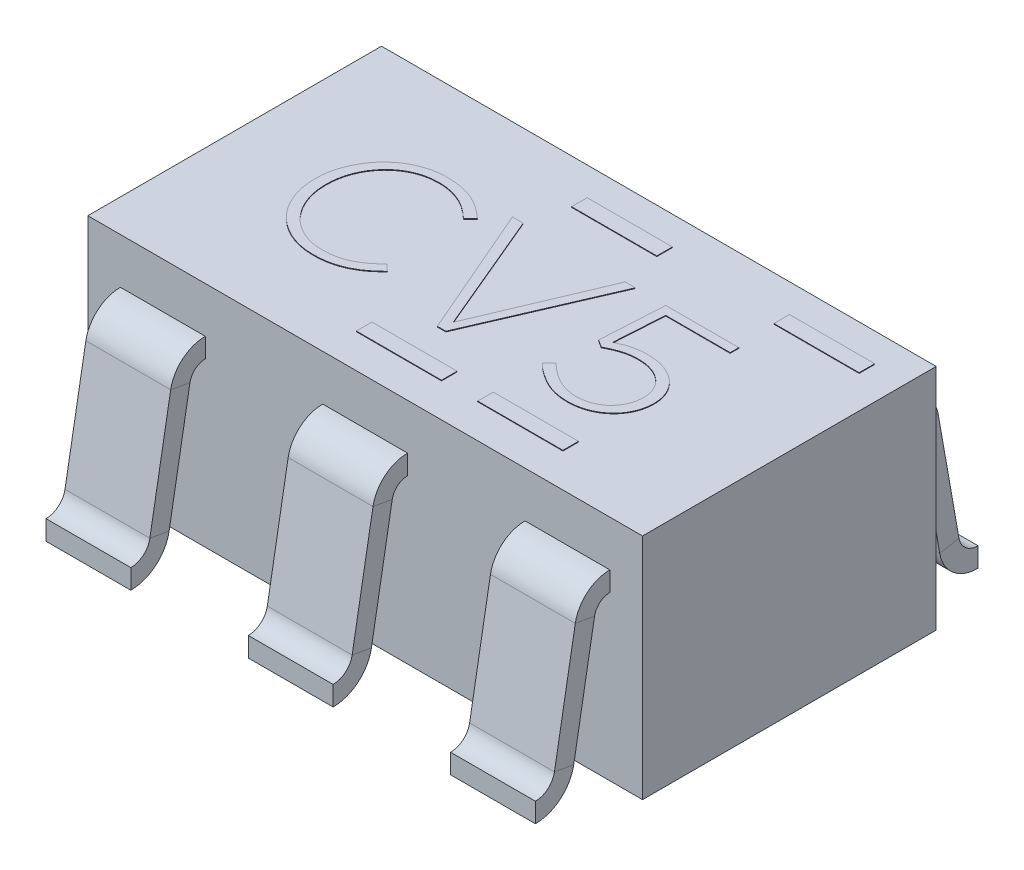
SolidWorks part; units mm, degrees
ref_plane "Front Plane" through (0, 0, 0) normal (0, 0, 1) x (1, 0, 0)
ref_plane "Top Plane" through (0, 0, 0) normal (0, 1, 0) x (1, 0, 0)
ref_plane "Right Plane" through (0, 0, 0) normal (1, 0, 0) x (0, 0, -1)
sketch "Sketch1" plane through (0, 0, 0) normal (0, 1, 0) x (1, 0, 0)
  line L1 (-1.0795, 0.5715) -> (1.0795, 0.5715)
  line L2 (-1.0795, 0.5715) -> (-1.0795, -0.5715)
  line L3 (-1.0795, -0.5715) -> (1.0795, -0.5715)
  line L4 (1.0795, 0.5715) -> (1.0795, -0.5715)
  point P4 (1.0795, 0)
  point P6 (0, 0.5715)
  dimension "D1" = 1.143
  dimension "D2" = 2.159
extrude "Boss-Extrude1" add sketch "Sketch1" along normal blind 0.889
sketch "Sketch2" plane through (0, 0, 0.5715) normal (0, 0, 1) x (1, 0, 0)
  line L0 (-1.0795, 0.889) -> (1.0795, 0.889) construction
  line L1 (-0.9525, 0.7112) -> (-0.6223, 0.7112)
  line L2 (-0.9525, 0.7112) -> (-0.9525, 0.635)
  line L3 (-0.9525, 0.635) -> (-0.6223, 0.635)
  line L4 (-0.6223, 0.7112) -> (-0.6223, 0.635)
  line L5 (-0.1651, 0.7112) -> (0.1651, 0.7112) construction
  line L6 (-0.1651, 0.7112) -> (-0.1651, 0.635) construction
  line L7 (-0.1651, 0.635) -> (0.1651, 0.635) construction
  line L8 (0.1651, 0.7112) -> (0.1651, 0.635) construction
  line L9 (0.6223, 0.7112) -> (0.9525, 0.7112)
  line L10 (0.6223, 0.7112) -> (0.6223, 0.635)
  line L11 (0.6223, 0.635) -> (0.9525, 0.635)
  line L12 (0.9525, 0.7112) -> (0.9525, 0.635)
  line L13 (-0.6223, 0.7112) -> (-0.1651, 0.7112) construction
  line L14 (0.1651, 0.7112) -> (0.6223, 0.7112) construction
  line L15 (1.0795, 0.889) -> (1.0795, 0) construction
  point P13 (0, 0.7112)
  point P16 (0, 0.889)
  dimension "D1" = 0.3302
  dimension "D2" = 0.1778
  dimension "D3" = 0.0762
  dimension "D4" = 0.127
sketch "Sketch3" plane through (0, 0, 0) normal (1, 0, 0) x (0, 0, -1)
  line L0 (-0.5715, 0.635) -> (-0.6223, 0.635) construction
  line L1 (-0.6223, 0.635) -> (-0.6311, 0.585) construction
  line L2 (-0.6311, 0.585) -> (-0.7122, 0.1251)
  line L3 (-0.7122, 0.1251) -> (-0.7343, 0) construction
  line L4 (-0.7343, 0) -> (-0.8613, 0) construction
  line L5 (-0.5715, 0) -> (0.5715, 0) construction
  arc A0 (-0.7122, 0.1251) -> (-0.8613, 0) centre (-0.8613, 0.1514) cw
  arc A1 (-0.6311, 0.585) -> (-0.5715, 0.635) centre (-0.5715, 0.5745) cw
  dimension "D1" = 0.0508
  dimension "D2" = 0.127
  dimension "D3" = 100
sweep "Sweep1" add profiles "Sketch2" path "Sketch3"
mirror "Mirror1" about plane through (0, 0, 0) normal (0, 0, 1) of "Sweep1"
sketch "Sketch4" plane through (0, 0, 0.5715) normal (0, 0, 1) x (1, 0, 0)
  line L1 (-0.1651, 0.635) -> (0.1651, 0.635)
  line L2 (-0.1651, 0.635) -> (-0.1651, 0.7112)
  line L3 (-0.1651, 0.7112) -> (0.1651, 0.7112)
  line L4 (0.1651, 0.635) -> (0.1651, 0.7112)
sweep "Sweep2" add profiles "Sketch4" path "Sketch3<2>"
sketch "Sketch3<2>" plane through (0, 0, 0) normal (1, 0, 0) x (0, 0, -1) same geometry as "Sketch3"
sketch "Sketch5" plane through (0, 0.889, 0) normal (0, 1, 0) x (1, 0, 0)
  line L0 (-1.1948, -0.2598) -> (1.0795, -0.2598) construction
  line L2 (1.0795, -0.5715) -> (1.0795, 0.5715) construction
  line L3 (0.6223, 0.7062) -> (0.9525, 0.7062) construction
  line L4 (-0.1658, 0.4585) -> (0.1658, 0.4585)
  line L5 (-0.1658, 0.4585) -> (-0.1658, 0.3979)
  line L6 (-0.1658, 0.3979) -> (0.1658, 0.3979)
  line L7 (0.1658, 0.4585) -> (0.1658, 0.3979)
  line L8 (-0.1658, -0.3795) -> (0.1658, -0.3795)
  line L9 (-0.1658, -0.3795) -> (-0.1658, -0.44)
  line L10 (-0.1658, -0.44) -> (0.1658, -0.44)
  line L11 (0.1658, -0.3795) -> (0.1658, -0.44)
  line L12 (0.3067, -0.3795) -> (0.6384, -0.3795)
  line L13 (0.3067, -0.3795) -> (0.3067, -0.44)
  line L14 (0.3067, -0.44) -> (0.6384, -0.44)
  line L15 (0.6384, -0.3795) -> (0.6384, -0.44)
  line L16 (0.6216, 0.4585) -> (0.9532, 0.4585)
  line L17 (0.6216, 0.4585) -> (0.6216, 0.3979)
  line L18 (0.6216, 0.3979) -> (0.9532, 0.3979)
  line L19 (0.9532, 0.4585) -> (0.9532, 0.3979)
  text T0 "CV5" font "Gotham Light" height 0.508
  point P2 (-1.1948, -0.2598)
  point P3 (0.7874, 0.4585)
  point P23 (0, -0.3795)
  point P24 (0, 0.3979)
  point P25 (0.3703, -0.4218)
  point P26 (1.0128, 0.3534)
  point P27 (0.2663, 0.3406)
  point P28 (0, 0)
  point P30 (0.7175, 0.3448)
  point P31 (0.1502, 0.3251)
  point P32 (0, 0)
  point P33 (0, 0)
  point P36 (0.7874, 0.7062)
  point P37 (0, 0)
  point P38 (-0.1658, -0.44)
extrude "Boss-Extrude2" add sketch "Sketch5" along normal blind 0.0025
